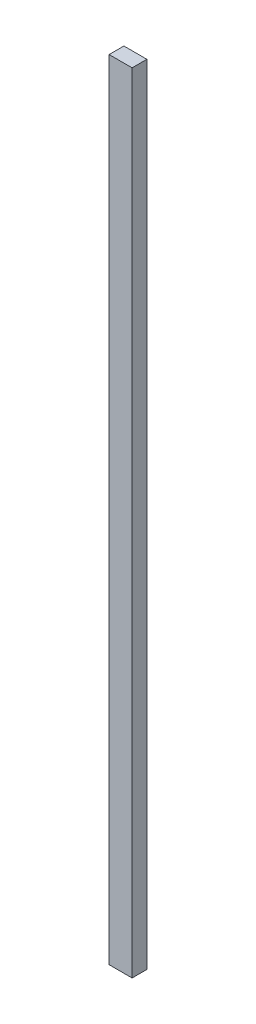
SolidWorks part; units mm, degrees
ref_plane "Front Plane" through (0, 0, 0) normal (0, 0, 1) x (1, 0, 0)
ref_plane "Top Plane" through (0, 0, 0) normal (0, 1, 0) x (1, 0, 0)
ref_plane "Right Plane" through (0, 0, 0) normal (1, 0, 0) x (0, 0, -1)
sketch "Sketch1" plane through (0, 0, 0) normal (0, 1, 0) x (1, 0, 0)
  line L1 (-35, 22.5) -> (35, 22.5)
  line L2 (-35, 22.5) -> (-35, -22.5)
  line L3 (-35, -22.5) -> (35, -22.5)
  line L4 (35, 22.5) -> (35, -22.5)
  line L5 (-35, 22.5) -> (35, -22.5) construction
  line L6 (-35, -22.5) -> (35, 22.5) construction
  point P0 (0, 0)
  dimension "D1" = 45
  dimension "D2" = 70
extrude "Shape" add sketch "Sketch1" along normal blind 2400
